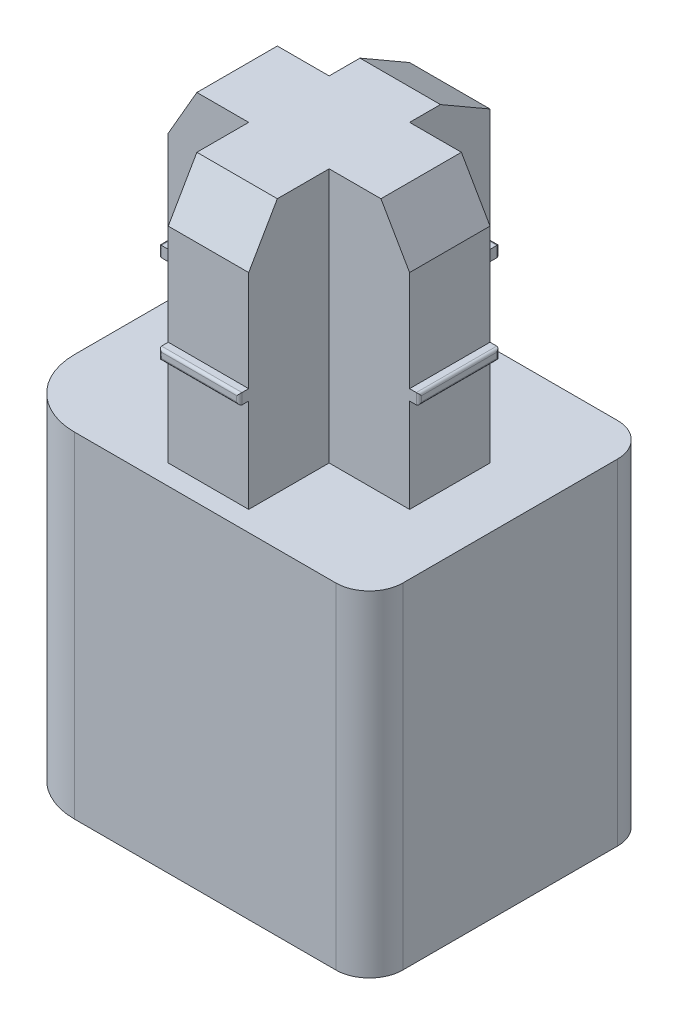
SolidWorks part; units mm, degrees
ref_plane "Front Plane" through (0, 0, 0) normal (0, 0, 1) x (1, 0, 0)
ref_plane "Top Plane" through (0, 0, 0) normal (0, 1, 0) x (1, 0, 0)
ref_plane "Right Plane" through (0, 0, 0) normal (1, 0, 0) x (0, 0, -1)
sketch "Sketch1" plane through (0, 0, 0) normal (0, 1, 0) x (1, 0, 0)
  line L1 (-3.429, 2.667) -> (3.429, 2.667)
  line L2 (-3.429, 2.667) -> (-3.429, -2.667)
  line L3 (-3.429, -2.667) -> (3.429, -2.667)
  line L4 (3.429, 2.667) -> (3.429, -2.667)
  line L5 (-3.429, 2.667) -> (3.429, -2.667) construction
  line L6 (-3.429, -2.667) -> (3.429, 2.667) construction
  point P0 (0, 0)
  dimension "D1" = 6.858
  dimension "D2" = 5.334
extrude "Boss-Extrude1" add sketch "Sketch1" along normal blind 6.35
sketch "Sketch2" plane through (0, 6.35, 0) normal (0, 1, 0) x (1, 0, 0)
  line L1 (-2.286, 0.762) -> (2.286, 0.762)
  line L2 (-2.286, 0.762) -> (-2.286, -0.762)
  line L3 (-2.286, -0.762) -> (2.286, -0.762)
  line L4 (2.286, 0.762) -> (2.286, -0.762)
  line L5 (-2.286, 0.762) -> (2.286, -0.762) construction
  line L6 (-2.286, -0.762) -> (2.286, 0.762) construction
  line L7 (-0.762, 2.286) -> (0.762, 2.286)
  line L8 (-0.762, 2.286) -> (-0.762, -2.286)
  line L9 (-0.762, -2.286) -> (0.762, -2.286)
  line L10 (0.762, 2.286) -> (0.762, -2.286)
  line L11 (-0.762, 2.286) -> (0.762, -2.286) construction
  line L12 (-0.762, -2.286) -> (0.762, 2.286) construction
  point P0 (0, 0)
  point P6 (0, 0)
  dimension "D1" = 1.524
  dimension "D2" = 1.524
  dimension "D3" = 4.572
  dimension "D4" = 4.572
extrude "Boss-Extrude2" add sketch "Sketch2" along normal blind 4.826 contours L10 L1 L8 L3 | L1 L10 L3 L4 | L10 L7 L8 L1 | L8 L1 L2 L3 | L10 L3 L8 L9
chamfer "Chamfer1" distance 0.9398 angle 30 4 edges at (2.286, 11.176, 0) (0, 11.176, -2.286) (-2.286, 11.176, 0) (0, 11.176, 2.286)
sketch "Sketch3" plane through (0, 11.176, 0) normal (0, 1, 0) x (1, 0, 0)
  line L1 (-2.4638, 0.762) -> (2.4638, 0.762)
  line L2 (-2.4638, 0.762) -> (-2.4638, -0.762)
  line L3 (-2.4638, -0.762) -> (2.4638, -0.762)
  line L4 (2.4638, 0.762) -> (2.4638, -0.762)
  line L5 (-2.4638, 0.762) -> (2.4638, -0.762) construction
  line L6 (-2.4638, -0.762) -> (2.4638, 0.762) construction
  line L7 (-0.762, -2.4638) -> (0.762, -2.4638)
  line L8 (-0.762, -2.4638) -> (-0.762, 2.4638)
  line L9 (-0.762, 2.4638) -> (0.762, 2.4638)
  line L10 (0.762, -2.4638) -> (0.762, 2.4638)
  line L11 (-0.762, -2.4638) -> (0.762, 2.4638) construction
  line L12 (-0.762, 2.4638) -> (0.762, -2.4638) construction
  point P0 (0, 0)
  point P6 (0, 0)
  line M5 (0.762, -0.762) -> (1.7434, -0.762)
  line M6 (1.7434, -0.762) -> (1.7434, 0.762)
  line M7 (1.7434, 0.762) -> (0.762, 0.762)
  line M8 (0.762, 0.762) -> (0.762, 1.3462)
  line M9 (0.762, 1.3462) -> (-0.762, 1.3462)
  line M10 (-0.762, 1.3462) -> (-0.762, 0.762)
  line M11 (-0.762, 0.762) -> (-1.7434, 0.762)
  line M12 (-1.7434, 0.762) -> (-1.7434, -0.762)
  line M13 (-1.7434, -0.762) -> (-0.762, -0.762)
  line M14 (-0.762, -0.762) -> (-0.762, -1.7434)
  line M15 (-0.762, -1.7434) -> (0.762, -1.7434)
  line M16 (0.762, -1.7434) -> (0.762, -0.762)
  dimension "D1" = 1.524
  dimension "D2" = 1.524
  dimension "D3" = 4.9276
  dimension "D4" = 4.9276
extrude "Boss-Extrude3" add sketch "Sketch3" along normal blind 0.2032 from offset 3.048 contours L4 L1 L3 M6 | L10 M5 M6 M7 | L10 L9 L8 M9 | L1 M10 M8 M9 | L3 L10 L1 L8 | L8 M13 M11 M12 | L2 L3 L1 M12 | L3 M14 M15 M16 | L7 L10 L8 M15 offset against normal yes
sketch "Sketch4" plane through (0, 0, 0) normal (0, -1, 0) x (1, 0, 0)
  line L1 (2.159, -0.762) -> (-2.159, -0.762)
  line L2 (2.159, -0.762) -> (2.159, 0.762)
  line L3 (2.159, 0.762) -> (-2.159, 0.762)
  line L4 (-2.159, -0.762) -> (-2.159, 0.762)
  line L5 (2.159, -0.762) -> (-2.159, 0.762) construction
  line L6 (2.159, 0.762) -> (-2.159, -0.762) construction
  line L7 (0.762, 2.159) -> (-0.762, 2.159)
  line L8 (0.762, 2.159) -> (0.762, -2.159)
  line L9 (0.762, -2.159) -> (-0.762, -2.159)
  line L10 (-0.762, 2.159) -> (-0.762, -2.159)
  line L11 (0.762, 2.159) -> (-0.762, -2.159) construction
  line L12 (0.762, -2.159) -> (-0.762, 2.159) construction
  point P0 (0, 0)
  point P6 (0, 0)
  dimension "D1" = 1.524
  dimension "D2" = 1.524
  dimension "D3" = 4.318
  dimension "D4" = 4.318
extrude "Cut-Extrude1" cut sketch "Sketch4" against normal blind 3.556 contours L10 L3 L4 L1 | L3 L10 L1 L8 | L3 L8 L1 L2 | L1 L10 L9 L8 | L7 L10 L3 L8
sketch "Sketch5" plane through (0, 0, 2.159) normal (0, 0, -1) x (-1, 0, 0)
  line L0 (-0.762, 3.556) -> (-0.762, 0) construction
  line L5 (-0.762, 1.778) -> (0.762, 1.778)
  line L6 (-0.762, 1.778) -> (-0.762, 2.921)
  line L7 (-0.762, 2.921) -> (0.762, 2.921)
  line L8 (0.762, 1.778) -> (0.762, 2.921)
  line L9 (-0.762, 1.778) -> (0.762, 2.921) construction
  line L10 (-0.762, 2.921) -> (0.762, 1.778) construction
  line L11 (0.762, 3.556) -> (0.762, 0) construction
  point P4 (0, 2.3495)
  dimension "D1" = 1.143
  dimension "D2" = 1.778
extrude "Boss-Extrude4" add sketch "Sketch5" along normal blind 0.254
fillet "Fillet1" radius 0.127 2 edges at (0, 2.921, 1.905) (0, 1.778, 1.905)
fillet "Fillet2" radius 0.0508 16 edges at (-0.762, 8.2296, -2.4638) (0.762, 8.2296, -2.4638) (0, 8.128, -2.4638) (0, 8.3312, -2.4638) (2.4638, 8.2296, -0.762) (2.4638, 8.2296, 0.762) (0.762, 8.2296, 2.4638) (-0.762, 8.2296, 2.4638) (-2.4638, 8.2296, 0.762) (-2.4638, 8.2296, -0.762) (-2.4638, 8.3312, 0) (-2.4638, 8.128, 0) (2.4638, 8.128, 0) (2.4638, 8.3312, 0) (0, 8.128, 2.4638) (0, 8.3312, 2.4638)
fillet "Fillet3" radius 0.635 3 edges at (-3.429, 3.175, -2.667) (3.429, 3.175, -2.667) (3.429, 3.175, 2.667)
fillet "Fillet4" radius 0.254 12 edges at (-1.4605, 0, 0.762) (-2.159, 0, 0) (-1.4605, 0, -0.762) (-0.762, 0, -1.4605) (0, 0, -2.159) (0.762, 0, -1.4605) (1.4605, 0, -0.762) (2.159, 0, 0) (1.4605, 0, 0.762) (0.762, 0, 1.4605) (0, 0, 2.159) (-0.762, 0, 1.4605)
fillet "Fillet5" radius 0.254 8 edges at (-0.8364, 0.0744, -0.8364) (0.8364, 0.0744, -0.8364) (0.8364, 0.0744, 0.8364) (-0.8364, 0.0744, 0.8364) (-0.762, 1.905, -0.762) (0.762, 1.905, -0.762) (0.762, 1.905, 0.762) (-0.762, 1.905, 0.762)
fillet "Fillet6" radius 1.27 1 edges at (-3.429, 3.175, 2.667)
